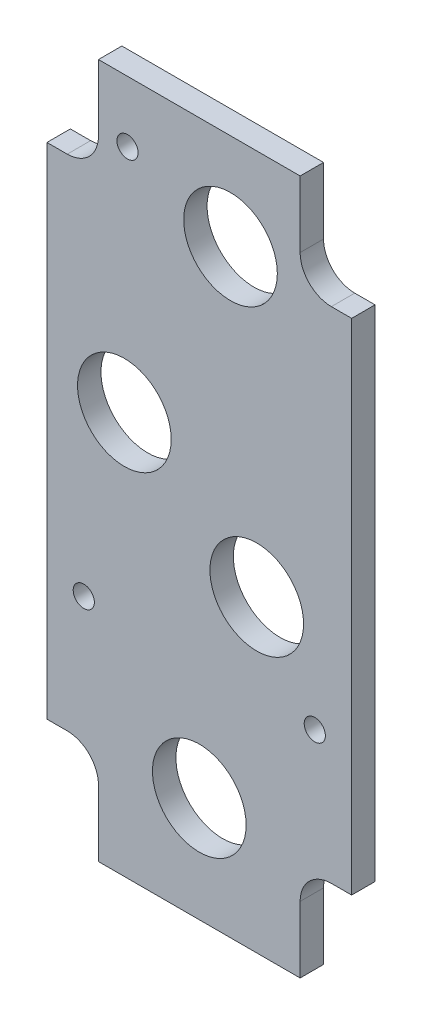
SolidWorks part; units mm, degrees
material "Acrylic (Medium-high impact)"
ref_plane "Front Plane" through (0, 0, 0) normal (0, 0, 1) x (1, 0, 0)
ref_plane "Top Plane" through (0, 0, 0) normal (0, 1, 0) x (1, 0, 0)
ref_plane "Right Plane" through (0, 0, 0) normal (1, 0, 0) x (0, 0, -1)
sketch "Sketch1" plane through (0, 0, -5.842) normal (0, 0, 1) x (1, 0, 0)
  line L24 (-20.5105, -128.5875) -> (-20.5105, -142.0812)
  line L25 (-20.5105, -142.0812) -> (20.5105, -142.0812)
  line L26 (20.5105, -142.0812) -> (20.5105, -128.5875)
  line L27 (26.8605, -122.2375) -> (30.988, -122.2375)
  line L28 (30.988, -122.2375) -> (30.988, -20.6375)
  line L29 (30.988, -20.6375) -> (26.8605, -20.6375)
  line L30 (20.5105, -14.2875) -> (20.5105, -0.7938)
  line L31 (20.5105, -0.7938) -> (-20.5105, -0.7938)
  line L32 (-20.5105, -0.7938) -> (-20.5105, -14.2875)
  line L33 (-26.8605, -20.6375) -> (-30.988, -20.6375)
  line L34 (-30.988, -20.6375) -> (-30.988, -122.2375)
  line L35 (-30.988, -122.2375) -> (-26.8605, -122.2375)
  arc A8 (-20.5105, -128.5875) -> (-26.8605, -122.2375) centre (-26.8605, -128.5875) ccw
  arc A9 (26.8605, -122.2375) -> (20.5105, -128.5875) centre (26.8605, -128.5875) ccw
  arc A10 (20.5105, -14.2875) -> (26.8605, -20.6375) centre (26.8605, -14.2875) ccw
  arc A11 (-26.8605, -20.6375) -> (-20.5105, -14.2875) centre (-26.8605, -14.2875) ccw
extrude "Boss-Extrude1" add sketch "Sketch1" along normal blind 4.7625
hole_wizard "#6 Clearance Hole1" positions "Sketch3" profile "Sketch2" hole size "#6" standard "ANSI Inch" end condition up to next
sketch "Sketch3" plane through (0, 0, -1.0795) normal (0, 0, 1) x (1, 0, 0)
  point P0 (-14.605, -13.208)
  point P4 (-23.495, -96.8375)
  point P6 (23.495, -96.8375)
sketch "Sketch2" plane through (-14.605, -13.208, -1.0795) normal (1, 0, 0) x (0, -1, 0)
  line L0 (0, 0) -> (0, 4.7625)
  line L1 (0, 4.7625) -> (2.1526, 4.7625)
  line L2 (2.1526, 4.7625) -> (2.1527, 0)
  line L5 (2.1527, 0) -> (0, 0)
  line L11 (0, -6.35) -> (0, 107.95) construction
  dimension "Thru Hole Dia." = 4.3053
  dimension "Thru Hole Depth" = 4.7625
hole_wizard "3/4 (0.75) Diameter Hole1" positions "Sketch5" profile "Sketch4" hole size "3/4" standard "ANSI Inch" end condition up to next
sketch "Sketch5" plane through (0, 0, -1.0795) normal (0, 0, 1) x (1, 0, 0)
  point P0 (-15.24, -60.325)
  point P2 (6.35, -20.32)
  point P4 (11.684, -79.375)
  point P6 (0, -120.65)
sketch "Sketch4" plane through (-15.24, -60.325, -1.0795) normal (1, 0, 0) x (0, -1, 0)
  line L0 (0, 0) -> (0, 4.7625)
  line L1 (0, 4.7625) -> (9.525, 4.7625)
  line L2 (9.525, 4.7625) -> (9.525, 0)
  line L5 (9.525, 0) -> (0, 0)
  line L11 (0, -6.35) -> (0, 107.95) construction
  dimension "Thru Hole Dia." = 19.05
  dimension "Thru Hole Depth" = 4.7625
